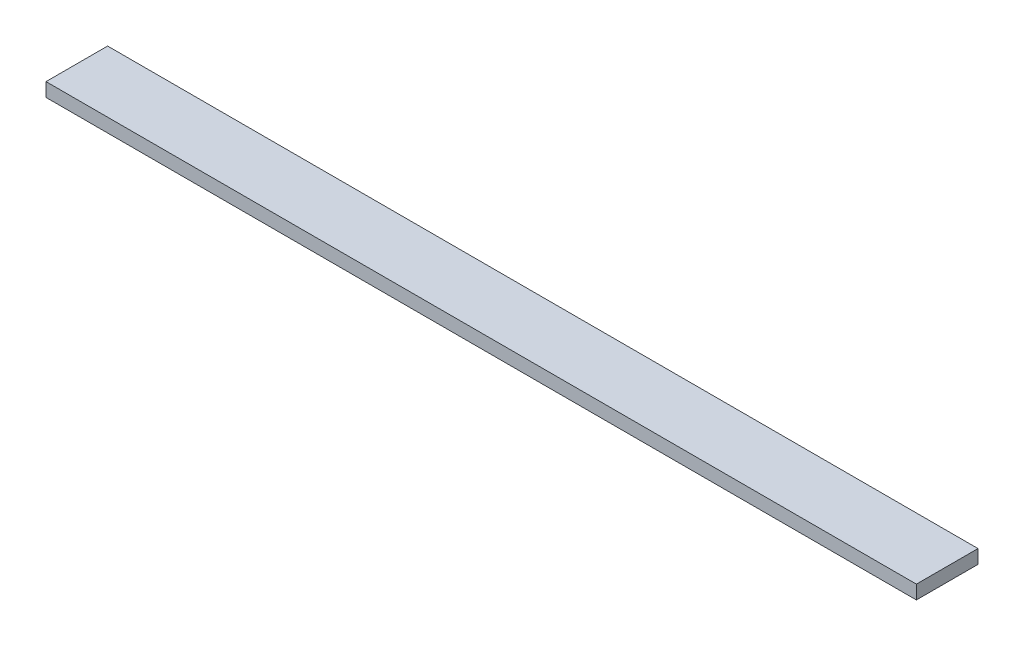
SolidWorks part; units mm, degrees
material "Oak"
ref_plane "Front Plane" through (0, 0, 0) normal (0, 0, 1) x (1, 0, 0)
ref_plane "Top Plane" through (0, 0, 0) normal (0, 1, 0) x (1, 0, 0)
ref_plane "Right Plane" through (0, 0, 0) normal (1, 0, 0) x (0, 0, -1)
sketch "Sketch1" plane through (0, 0, 0) normal (0, 1, 0) x (1, 0, 0)
  line L1 (0, 0) -> (805, 0)
  line L2 (0, 0) -> (0, 56.98)
  line L3 (0, 56.98) -> (805, 56.98)
  line L4 (805, 0) -> (805, 56.98)
  dimension "D1" = 56.98
  dimension "D2" = 805
extrude "Boss-Extrude1" add sketch "Sketch1" along normal blind 12.7
